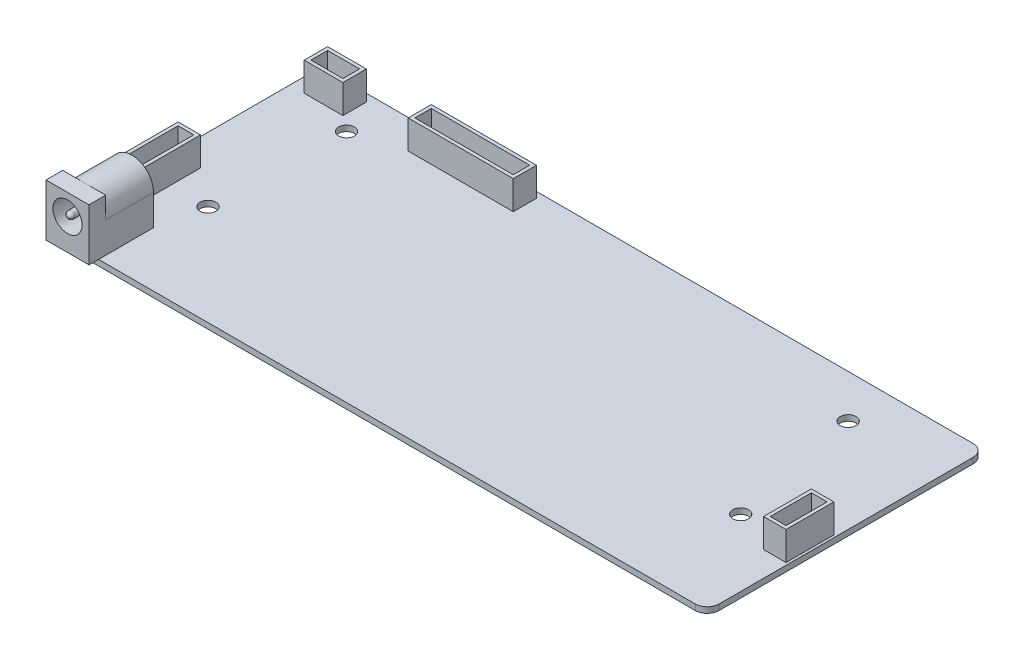
SolidWorks part; units mm, degrees
ref_plane "Front Plane" through (0, 0, 0) normal (0, 0, 1) x (1, 0, 0)
ref_plane "Top Plane" through (0, 0, 0) normal (0, 1, 0) x (1, 0, 0)
ref_plane "Right Plane" through (0, 0, 0) normal (1, 0, 0) x (0, 0, -1)
sketch "Sketch1" plane through (0, 0, 0) normal (0, 1, 0) x (1, 0, 0)
  line L0 (-69.5, -29.075) -> (69.5, 29.075) construction
  line L1 (-67, 29.075) -> (67, 29.075)
  line L2 (-69.5, 26.575) -> (-69.5, -26.575)
  line L3 (-67, -29.075) -> (67, -29.075)
  line L4 (69.5, 26.575) -> (69.5, -26.575)
  arc A0 (67, 29.075) -> (69.5, 26.575) centre (67, 26.575) cw
  arc A1 (67, -29.075) -> (69.5, -26.575) centre (67, -26.575) ccw
  arc A2 (-69.5, -26.575) -> (-67, -29.075) centre (-67, -26.575) ccw
  arc A3 (-67, 29.075) -> (-69.5, 26.575) centre (-67, 26.575) ccw
  circle A4 centre (-55.15, 20.075) radius 1.65
  circle A5 centre (49.85, 20.075) radius 1.65
  circle A6 centre (55.5, -8.075) radius 1.65
  circle A7 centre (-56, -8.075) radius 1.65
  point P17 (-69.5, 29.075)
  dimension "D3" = 2.5
  dimension "D12" = 3.3
  dimension "D1" = 58.15
  dimension "D2" = 139
  dimension "D4" = 19.65
  dimension "D5" = 9
  dimension "D6" = 14
  dimension "D7" = 21
  dimension "D8" = 21
  dimension "D9" = 13.5
  dimension "D10" = 14.35
  dimension "D11" = 9
extrude "Boss-Extrude1" add sketch "Sketch1" along normal blind 0.6 and the other way blind 0.6
sketch "Sketch2" plane through (0, 0.6, 0) normal (0, 1, 0) x (1, 0, 0)
  line L0 (67, 29.075) -> (-67, 29.075) construction
  line L1 (-66.5, 27.475) -> (-58.4, 27.475)
  line L2 (-66.5, 27.475) -> (-66.5, 22.575)
  line L3 (-66.5, 22.575) -> (-58.4, 22.575)
  line L4 (-58.4, 27.475) -> (-58.4, 22.575)
  line L5 (-45.15, 27.825) -> (-23.15, 27.825)
  line L6 (-45.15, 27.825) -> (-45.15, 22.975)
  line L7 (-45.15, 22.975) -> (-23.15, 22.975)
  line L8 (-23.15, 27.825) -> (-23.15, 22.975)
  line L9 (-69.5, 26.575) -> (-69.5, -26.575) construction
  line L10 (-65.8, 26.775) -> (-66.5, 27.475) construction
  line L11 (-65.8, 26.775) -> (-59.1, 26.775)
  line L12 (-65.8, 26.775) -> (-65.8, 23.275)
  line L13 (-65.8, 23.275) -> (-59.1, 23.275)
  line L14 (-59.1, 26.775) -> (-59.1, 23.275)
  line L15 (-65.8, 23.275) -> (-66.5, 22.575) construction
  line L16 (-59.1, 23.275) -> (-58.4, 22.575) construction
  line L17 (-59.1, 26.775) -> (-58.4, 27.475) construction
  line L18 (-44.45, 27.125) -> (-45.15, 27.825) construction
  line L19 (-44.45, 27.125) -> (-23.85, 27.125)
  line L20 (-44.45, 27.125) -> (-44.45, 23.675)
  line L21 (-44.45, 23.675) -> (-23.85, 23.675)
  line L22 (-23.85, 27.125) -> (-23.85, 23.675)
  line L23 (-44.45, 23.675) -> (-45.15, 22.975) construction
  line L24 (-23.85, 23.675) -> (-23.15, 22.975) construction
  line L25 (-23.85, 27.125) -> (-23.15, 27.825) construction
  line L26 (-62.45, 26.775) -> (-62.45, 27.475) construction
  line L27 (-34.15, 27.125) -> (-34.15, 27.825) construction
  line L28 (-66.15, -2.525) -> (-66.15, -1.825) construction
  line L29 (-67.8, -2.525) -> (-64.5, -2.525)
  line L30 (-67.8, -2.525) -> (-67.8, -15.125)
  line L31 (-67.8, -15.125) -> (-64.5, -15.125)
  line L32 (-64.5, -2.525) -> (-64.5, -15.125)
  line L33 (-68.5, -1.825) -> (-63.8, -1.825)
  line L34 (-68.5, -1.825) -> (-68.5, -15.825)
  line L35 (-68.5, -15.825) -> (-63.8, -15.825)
  line L36 (-63.8, -1.825) -> (-63.8, -15.825)
  line L37 (-67.8, -2.525) -> (-68.5, -1.825) construction
  line L38 (-63.8, -1.825) -> (-64.5, -2.525) construction
  line L39 (-64.5, -15.125) -> (-63.8, -15.825) construction
  line L40 (-68.5, -15.825) -> (-67.8, -15.125) construction
  line L41 (-67, -29.075) -> (67, -29.075) construction
  line L42 (68.3, -11.375) -> (69, -12.075) construction
  line L43 (64.3, -2.075) -> (69, -2.075)
  line L44 (64.3, -2.075) -> (64.3, -12.075)
  line L45 (64.3, -12.075) -> (69, -12.075)
  line L46 (69, -2.075) -> (69, -12.075)
  line L47 (65, -2.775) -> (68.3, -2.775)
  line L48 (65, -2.775) -> (65, -11.375)
  line L49 (65, -11.375) -> (68.3, -11.375)
  line L50 (68.3, -2.775) -> (68.3, -11.375)
  line L51 (69, -2.075) -> (68.3, -2.775) construction
  line L52 (65, -2.775) -> (64.3, -2.075) construction
  line L53 (64.3, -12.075) -> (65, -11.375) construction
  line L54 (66.65, -2.775) -> (66.65, -2.075) construction
  line L55 (69.5, -26.575) -> (69.5, 26.575) construction
  dimension "D1" = 1.6
  dimension "D2" = 3
  dimension "D3" = 4.9
  dimension "D4" = 8.1
  dimension "D5" = 0.7
  dimension "D6" = 0.7
  dimension "D7" = 1.25
  dimension "D8" = 13.25
  dimension "D9" = 4.85
  dimension "D10" = 22
  dimension "D11" = 1
  dimension "D12" = 14
  dimension "D13" = 13.25
  dimension "D14" = 4.7
  dimension "D15" = 10
  dimension "D16" = 4.7
  dimension "D17" = 0.5
  dimension "D18" = 17
extrude "Boss-Extrude2" add sketch "Sketch2" along normal blind 6
sketch "Sketch3" plane through (0, 0.6, 0) normal (0, 1, 0) x (1, 0, 0)
  line L1 (-57.9, -17.575) -> (-66.9, -17.575)
  line L2 (-57.9, -17.575) -> (-57.9, -31.075)
  line L3 (-57.9, -31.075) -> (-66.9, -31.075)
  line L4 (-66.9, -17.575) -> (-66.9, -31.075)
  line L5 (-67, -29.075) -> (67, -29.075) construction
  line L6 (-69.5, 26.575) -> (-69.5, -26.575) construction
  dimension "D1" = 2
  dimension "D2" = 9
  dimension "D3" = 13.5
  dimension "D4" = 2.6
extrude "Boss-Extrude3" add sketch "Sketch3" along normal blind 10.9
sketch "Sketch4" plane through (0, 0, 17.575) normal (0, 0, -1) x (-1, 0, 0)
  line L0 (57.9, 11.5) -> (66.9, 11.5) construction
  line L1 (57.9, 11.5) -> (57.9, 0.6) construction
  line L2 (66.9, 11.5) -> (66.9, 0.6) construction
  line L3 (57.9, 7) -> (57.9, 11.5)
  line L4 (57.9, 11.5) -> (66.9, 11.5)
  line L5 (66.9, 11.5) -> (66.9, 7)
  arc A0 (66.9, 7) -> (57.9, 7) centre (62.4, 7) ccw
  line M2 (66.9, 0.6) -> (66.9, 11.5)
  line M3 (66.9, 11.5) -> (57.9, 11.5)
  line M4 (57.9, 11.5) -> (57.9, 0.6)
extrude "Cut-Extrude1" cut sketch "Sketch4" against normal blind 10 contours A0 L4 M4 | A0 M2 M3 region at (-65.8948, 10.4948, 17.575) region at (-58.9052, 10.4948, 17.575)
sketch "Sketch5" plane through (0, 0, 31.075) normal (0, 0, 1) x (1, 0, 0)
  line L0 (-62.4, 11.5) -> (-62.4, 7.1) construction
  line L1 (-66.9, 11.5) -> (-57.9, 11.5) construction
  circle A0 centre (-62.4, 7.1) radius 3.05
  circle A1 centre (-62.4, 7.1) radius 0.75
  point P3 (-62.4, 10.15)
  dimension "D1" = 6.1
  dimension "D3" = 1.5
  dimension "D2" = 1.35
extrude "Cut-Extrude2" cut sketch "Sketch5" against normal blind 11.9
fillet "Fillet1" radius 0.75 1 edges at (-61.65, 7.1, 31.075)
